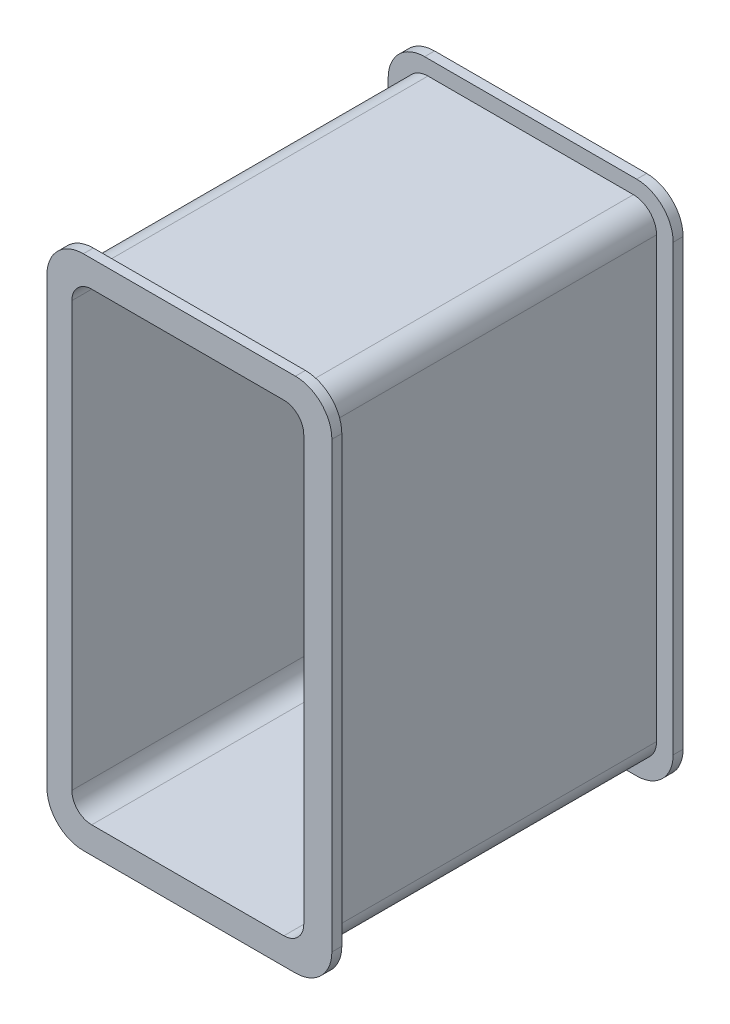
SolidWorks part; units mm, degrees
ref_plane "Front Plane" through (0, 0, 0) normal (1, 0, 0) x (0, 1, 0)
ref_plane "Top Plane" through (0, 0, 0) normal (0, 0, 1) x (0, 1, 0)
ref_plane "Right Plane" through (0, 0, 0) normal (0, 1, 0) x (-1, 0, 0)
sketch "Sketch1" plane through (0, 0, 0) normal (0, 0, 1) x (0, 1, 0)
  line L0 (7, 0) -> (139.4415, 0)
  line L1 (146.4415, 7) -> (146.4415, 69)
  line L2 (139.4415, 76) -> (7, 76)
  line L3 (0, 69) -> (0, 7)
  line L5 (151, 38) -> (151, 6)
  line L6 (3, 38) -> (3, 67.4812)
  line L7 (9, 73.4812) -> (137, 73.4812)
  line L8 (143, 67.4812) -> (143, 9.4812)
  line L9 (137, 3.4812) -> (9, 3.4812)
  line L10 (3, 9.4812) -> (3, 38)
  line L11 (3, 9.4812) -> (3, 38)
  line L12 (-5, 38.978) -> (-5, 70)
  line L13 (6, 81) -> (73.2207, 81)
  line L15 (73.2207, 81) -> (140, 81)
  line L16 (151, 70) -> (151, 38)
  line L17 (140, -5) -> (6, -5)
  line L20 (-5, 6) -> (-5, 70)
  arc A0 (3, 67.4812) -> (9, 73.4812) centre (9, 67.4812) cw
  arc A1 (137, 73.4812) -> (143, 67.4812) centre (137, 67.4812) cw
  arc A2 (143, 9.4812) -> (137, 3.4812) centre (137, 9.4812) cw
  arc A3 (9, 3.4812) -> (3, 9.4812) centre (9, 9.4812) cw
  arc A4 (7, 0) -> (0, 7) centre (7, 7) cw
  arc A5 (139.4415, 0) -> (146.4415, 7) centre (139.4415, 7) ccw
  arc A6 (146.4415, 69) -> (139.4415, 76) centre (139.4415, 69) ccw
  arc A7 (7, 76) -> (0, 69) centre (7, 69) ccw
  arc A8 (6, -5) -> (-5, 6) centre (6, 6) cw
  arc A9 (-5, 70) -> (6, 81) centre (6, 70) cw
  arc A10 (140, 81) -> (151, 70) centre (140, 70) cw
  arc A11 (140, -5) -> (151, 6) centre (140, 6) ccw
  point P0 (0, 0)
  point P22 (0, 0)
  point P31 (0, 0)
  point P44 (0, 0)
  point P45 (0, 0)
  dimension "D1" = 6
  dimension "D2" = 7
  dimension "D3" = 11
extrude "Boss-Extrude3" add sketch "Sketch1" along normal blind 100 contours L3 A4 L0 A5 L1 A6 L2 A7 | L6 A0 L7 A1 L8 A2 L9 A3 L10
extrude "Boss-Extrude4" add sketch "Sketch1<5>" against normal blind 3 contours A9 L13 L15 A10 L16 L5 A11 L17 A8 L20
sketch "Sketch1<5>" plane through (0, 0, 0) normal (0, 0, 1) x (0, 1, 0) same geometry as "Sketch1"
sketch "Sketch2" plane through (0, 0, 100) normal (0, 0, 1) x (1, 0, 0)
  line L0 (-67.4812, 143) -> (-9.4812, 143)
  line L1 (-3.4812, 137) -> (-3.4812, 9)
  line L2 (-9.4812, 3) -> (-67.4812, 3)
  line L3 (-73.4812, 9) -> (-73.4812, 137)
  line L4 (-70, 151) -> (-6, 151)
  line L5 (5, 140) -> (5, 6)
  line L6 (-6, -5) -> (-70, -5)
  line L7 (-81, 6) -> (-81, 140)
  arc A0 (-81, 6) -> (-70, -5) centre (-70, 6) ccw
  arc A1 (5, 6) -> (-6, -5) centre (-6, 6) cw
  arc A2 (5, 140) -> (-6, 151) centre (-6, 140) ccw
  arc A3 (-70, 151) -> (-81, 140) centre (-70, 140) ccw
  arc A4 (-73.4812, 9) -> (-67.4812, 3) centre (-67.4812, 9) ccw
  arc A5 (-3.4812, 9) -> (-9.4812, 3) centre (-9.4812, 9) cw
  arc A6 (-3.4812, 137) -> (-9.4812, 143) centre (-9.4812, 137) ccw
  arc A7 (-67.4812, 143) -> (-73.4812, 137) centre (-67.4812, 137) ccw
  dimension "D1" = 11
  dimension "D2" = 6
extrude "Boss-Extrude5" add sketch "Sketch2" along normal blind 3
sketch "Sketch5" plane through (-76, 0, 0) normal (-1, 0, 0) x (0, -1, 0)
  line L0 (0, 100) -> (0, 0) construction
  line L2 (-140, 100) -> (-6, 100) construction
  line L3 (-140, 103) -> (-6, 103) construction
  line L4 (-6, -3) -> (-140, -3) construction
  line L5 (-151, -3) -> (-151, 0) construction
  line L6 (5, -3) -> (5, 0) construction
  line L7 (-146.4415, 100) -> (-146.4415, 0) construction
  line L8 (-139.4415, 2.673) -> (-7, 2.673)
  line L9 (-139.4415, 100) -> (-139.4415, 0) construction
  line L10 (-7, 100) -> (-7, 0) construction
  dimension "D1" = 100
  dimension "D2" = 3
  dimension "D3" = 106
  dimension "D4" = 156
  dimension "D5" = 146.4415
sketch "Sketch6" plane through (0, 146.4415, 0) normal (0, 1, 0) x (-1, 0, 0)
  line L0 (7, 67.5438) -> (69, 67.5438)
  line L1 (7, 100) -> (7, 0) construction
  line L2 (69, 100) -> (69, 0) construction
  line L3 (0, 100) -> (0, 0) construction
  line L4 (76, 100) -> (76, 0) construction
  line L5 (-5, -3) -> (-5, 0) construction
  line L6 (81, -3) -> (81, 0) construction
  dimension "D1" = 76
  dimension "D2" = 86
